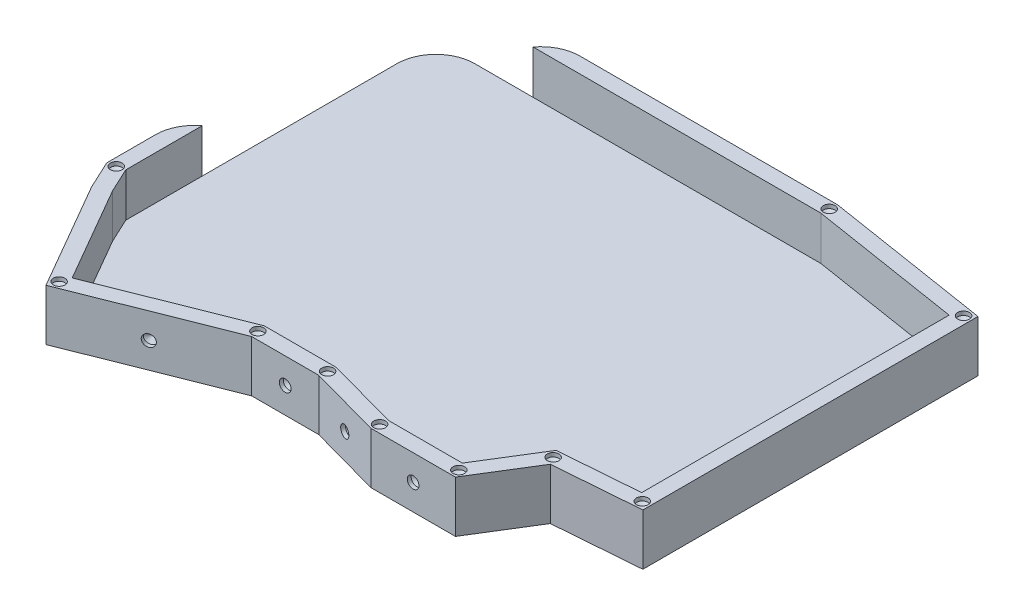
SolidWorks part; units mm, degrees
ref_plane "Front Plane" through (0, 0, 0) normal (0, 0, 1) x (1, 0, 0)
ref_plane "Top Plane" through (0, 0, 0) normal (0, 1, 0) x (1, 0, 0)
ref_plane "Right Plane" through (0, 0, 0) normal (1, 0, 0) x (0, 0, -1)
sketch "Sketch4"
  line L0 (261.3841, 490) -> (1306.7175, 490) construction
sketch "outline" plane through (0, 0, 0) normal (0, 1, 0) x (1, 0, 0)
  line L0 (23.1521, 111.8179) -> (23.1521, 32.6746) construction
  line L1 (23.1521, 32.6746) -> (26.0432, 26.4778) construction
  line L2 (26.0432, 26.4778) -> (40.0838, 2.1711) construction
  line L3 (40.0838, 2.1711) -> (75.1374, 16.0801) construction
  line L4 (75.1374, 16.0801) -> (93.8189, 16.0801) construction
  line L5 (93.8189, 16.0801) -> (112.2703, 10.9819) construction
  line L6 (112.2703, 10.9819) -> (130.9633, 10.9819) construction
  line L7 (130.9633, 10.9819) -> (140.1644, 25.8373) construction
  line L8 (140.1644, 25.8373) -> (160.3881, 27.4157) construction
  line L9 (160.3881, 27.4157) -> (160.3881, 105.6539) construction
  line L10 (160.3881, 105.6539) -> (121.5662, 111.8179) construction
  line L11 (121.5662, 111.8179) -> (23.1521, 111.8179) construction
  line L12 (22.7521, 112.2179) -> (22.7521, 32.5858)
  line L13 (22.7521, 32.5858) -> (25.6881, 26.2928)
  line L14 (25.6881, 26.2928) -> (39.9102, 1.6719)
  line L15 (39.9102, 1.6719) -> (75.2139, 15.6801)
  line L16 (75.2139, 15.6801) -> (93.7646, 15.6801)
  line L17 (93.7646, 15.6801) -> (112.216, 10.5819)
  line L18 (112.216, 10.5819) -> (131.1861, 10.5819)
  line L19 (131.1861, 10.5819) -> (140.3977, 25.4543)
  line L20 (140.3977, 25.4543) -> (160.7881, 27.0457)
  line L21 (160.7881, 27.0457) -> (160.7881, 105.9954)
  line L22 (160.7881, 105.9954) -> (121.5978, 112.2179)
  line L23 (121.5978, 112.2179) -> (22.7521, 112.2179)
  line L24 (18.7521, 116.2179) -> (18.7521, 31.6986)
  line L25 (18.7521, 31.6986) -> (22.1371, 24.4433)
  line L26 (22.1371, 24.4433) -> (38.1745, -3.3202)
  line L27 (38.1745, -3.3202) -> (75.9785, 11.6801)
  line L28 (75.9785, 11.6801) -> (93.2222, 11.6801)
  line L29 (93.2222, 11.6801) -> (111.6736, 6.5819)
  line L30 (111.6736, 6.5819) -> (133.4137, 6.5819)
  line L31 (133.4137, 6.5819) -> (142.7305, 21.6242)
  line L32 (142.7305, 21.6242) -> (164.7881, 23.3457)
  line L33 (164.7881, 23.3457) -> (164.7881, 109.4104)
  line L34 (164.7881, 109.4104) -> (121.9134, 116.2179)
  line L35 (121.9134, 116.2179) -> (18.7521, 116.2179)
  line L36 (23.9521, 111.0179) -> (23.9521, 32.852)
  line L37 (23.9521, 32.852) -> (26.7534, 26.8477)
  line L38 (26.7534, 26.8477) -> (40.431, 3.1695)
  line L39 (40.431, 3.1695) -> (74.9845, 16.8801)
  line L40 (74.9845, 16.8801) -> (93.9274, 16.8801)
  line L41 (93.9274, 16.8801) -> (112.3788, 11.7819)
  line L42 (112.3788, 11.7819) -> (130.5178, 11.7819)
  line L43 (130.5178, 11.7819) -> (139.6978, 26.6033)
  line L44 (139.6978, 26.6033) -> (159.5881, 28.1556)
  line L45 (159.5881, 28.1556) -> (159.5881, 104.9709)
  line L46 (159.5881, 104.9709) -> (121.5031, 111.0179)
  line L47 (121.5031, 111.0179) -> (23.9521, 111.0179)
  dimension "D1" = 137.236
  dimension "D3" = 4
  dimension "D4" = 1.2
  dimension "D2" = 0.4
extrude "Boss-Extrude1" add sketch "outline" along normal blind 13.2 contours L34 L35 L24 L25 L26 L27 L28 L29 L30 L31 L32 L33 L23 L22 L21 L20 L19 L18 L17 L16 L15 L14 L13 L12 region at (70.3327, 0, -114.3307)
extrude "Boss-Extrude3" add sketch "outline<4>" along normal blind 2 contours L22 L23 L12 L13 L14 L15 L16 L17 L18 L19 L20 L21 L47 L46 L45 L44 L43 L42 L41 L40 L39 L38 L37 L36 | L46 L47 L36 L37 L38 L39 L40 L41 L42 L43 L44 L45 region at (72.1749, 0, -112.0411) region at (89.8763, 0, -62.795)
sketch "outline<4>" plane through (0, 0, 0) normal (0, 1, 0) x (1, 0, 0) same geometry as "outline"
sketch "cutout" plane through (0, 0, 0) normal (0, 1, 0) x (1, 0, 0)
  line L0 (47.7521, 112.2179) -> (47.7521, 116.2179)
  line L1 (22.7521, 112.2179) -> (47.7521, 112.2179)
  line L2 (22.7521, 112.2179) -> (22.7521, 52.2179)
  line L3 (22.7521, 52.2179) -> (47.7521, 52.2179)
  line L4 (47.7521, 112.2179) -> (47.7521, 52.2179)
  line L6 (47.7521, 116.2179) -> (18.7521, 116.2179)
  line L7 (18.7521, 116.2179) -> (18.7521, 52.2179)
  line L9 (18.7521, 52.2179) -> (22.7521, 52.2179)
  dimension "D1" = 25
  dimension "D2" = 60
extrude "Cut-Extrude1" cut sketch "cutout" along normal through all contours L7 L9 L2 L1 L0 L6 region at (35.2521, 0, -112.9206)
sketch "Sketch15" plane through (6.331, 0, 15.9554) normal (0.3688, 0, 0.9295) x (0.9295, 0, -0.3688)
  line L0 (34.2587, 13.2) -> (74.9299, 0) construction
  point P6 (54.5943, 6.6)
sketch "Sketch16" plane through (0, 0, -11.6801) normal (0, 0, 1) x (1, 0, 0)
  line L0 (75.9785, 13.2) -> (93.2222, 0) construction
  point P6 (84.6003, 6.6)
sketch "Sketch17" plane through (9.6107, 0, -34.7825) normal (-0.2663, 0, 0.9639) x (0.9639, 0, 0.2663)
  line L0 (86.7445, 13.2) -> (105.8873, 0) construction
  point P6 (96.3159, 6.6)
sketch "Sketch18" plane through (0, 0, -6.5819) normal (0, 0, 1) x (1, 0, 0)
  line L0 (111.6736, 13.2) -> (133.4137, 0) construction
  point P6 (122.5436, 6.6)
hole_wizard "Ø3.0mm Dowel Hole6" positions "Sketch15" profile "Sketch20" hole size "Ø3.0" standard "ANSI Metric"
sketch "Sketch20" plane through (57.0765, 6.6, -4.18) normal (0, 1, 0) x (0.9295, 0, -0.3688)
  line L0 (0, 0) -> (0, 1.9013)
  line L1 (0, 1.9013) -> (1.5, 1)
  line L2 (1.5, 1) -> (1.5, 0)
  line L5 (1.5, 0) -> (0, 0)
  line L10 (0, 1.9013) -> (-1.5, 1) construction
  line L11 (0, -6.35) -> (0, 107.95) construction
  dimension "Hole Dia." = 3
  dimension "Hole Depth" = 1
  dimension "Drill Angle" = 118
hole_wizard "Ø3.0mm Dowel Hole7" positions "Sketch16" profile "Sketch21" hole size "Ø3.0" standard "ANSI Metric"
sketch "Sketch21" plane through (84.6003, 6.6, -11.6801) normal (1, 0, 0) x (0, -1, 0)
  line L0 (0, 0) -> (0, 1.9013)
  line L1 (0, 1.9013) -> (1.5, 1)
  line L2 (1.5, 1) -> (1.5, 0)
  line L5 (1.5, 0) -> (0, 0)
  line L10 (0, 1.9013) -> (-1.5, 1) construction
  line L11 (0, -6.35) -> (0, 107.95) construction
  dimension "Hole Dia." = 3
  dimension "Hole Depth" = 1
  dimension "Drill Angle" = 118
hole_wizard "Ø3.0mm Dowel Hole8" positions "Sketch17" profile "Sketch22" hole size "Ø3.0" standard "ANSI Metric"
sketch "Sketch22" plane through (102.4479, 6.6, -9.131) normal (0, 1, 0) x (0.9639, 0, 0.2663)
  line L0 (0, 0) -> (0, 1.9013)
  line L1 (0, 1.9013) -> (1.5, 1)
  line L2 (1.5, 1) -> (1.5, 0)
  line L5 (1.5, 0) -> (0, 0)
  line L10 (0, 1.9013) -> (-1.5, 1) construction
  line L11 (0, -6.35) -> (0, 107.95) construction
  dimension "Hole Dia." = 3
  dimension "Hole Depth" = 1
  dimension "Drill Angle" = 118
hole_wizard "Ø3.0mm Dowel Hole5" positions "Sketch18" profile "Sketch19" hole size "Ø3.0" standard "ANSI Metric"
sketch "Sketch19" plane through (122.5436, 6.6, -6.5819) normal (1, 0, 0) x (0, -1, 0)
  line L0 (0, 0) -> (0, 1.9013)
  line L1 (0, 1.9013) -> (1.5, 1)
  line L2 (1.5, 1) -> (1.5, 0)
  line L5 (1.5, 0) -> (0, 0)
  line L10 (0, 1.9013) -> (-1.5, 1) construction
  line L11 (0, -6.35) -> (0, 107.95) construction
  dimension "Hole Dia." = 3
  dimension "Hole Depth" = 1
  dimension "Drill Angle" = 118
sketch "Sketch29" plane through (0, 13.2, 0) normal (0, 1, 0) x (1, 0, 0)
  line L0 (18.7521, 31.6986) -> (22.7521, 32.5858) construction
  line L1 (22.7521, 32.5858) -> (38.1745, -3.3202) construction
  line L2 (38.1745, -3.3202) -> (39.9102, 1.6719) construction
  line L3 (39.9102, 1.6719) -> (75.9785, 11.6801) construction
  line L4 (75.9785, 11.6801) -> (75.2139, 15.6801) construction
  line L5 (75.2139, 15.6801) -> (93.2222, 11.6801) construction
  line L6 (93.2222, 11.6801) -> (93.7646, 15.6801) construction
  line L7 (93.7646, 15.6801) -> (111.6736, 6.5819) construction
  line L8 (111.6736, 6.5819) -> (112.216, 10.5819) construction
  line L9 (112.216, 10.5819) -> (133.4137, 6.5819) construction
  line L10 (133.4137, 6.5819) -> (131.1861, 10.5819) construction
  line L11 (131.1861, 10.5819) -> (142.7305, 21.6242) construction
  line L12 (142.7305, 21.6242) -> (140.3977, 25.4543) construction
  line L13 (140.3977, 25.4543) -> (164.7881, 23.3457) construction
  line L14 (164.7881, 23.3457) -> (160.7881, 27.0457) construction
  line L15 (160.7881, 27.0457) -> (164.7881, 109.4104) construction
  line L16 (164.7881, 109.4104) -> (160.7881, 105.9954) construction
  line L17 (160.7881, 105.9954) -> (121.9134, 116.2179) construction
  line L18 (121.9134, 116.2179) -> (121.5978, 112.2179) construction
  point P41 (20.7521, 32.1422)
  point P43 (39.0424, -0.8241)
  point P45 (75.5962, 13.6801)
  point P47 (93.4934, 13.6801)
  point P49 (111.9448, 8.5819)
  point P51 (132.2999, 8.5819)
  point P53 (141.5641, 23.5392)
  point P55 (162.7881, 25.1957)
  point P57 (162.7881, 107.7029)
  point P59 (121.7556, 114.2179)
hole_wizard "Ø3.0mm Dowel Hole9" positions "Sketch29" profile "Sketch31" hole size "Ø3.0" standard "ANSI Metric"
sketch "Sketch31" plane through (121.7556, 13.2, -114.2179) normal (1, 0, 0) x (0, 0, 1)
  line L0 (0, 0) -> (0, 1.9013)
  line L1 (0, 1.9013) -> (1.5, 1)
  line L2 (1.5, 1) -> (1.5, 0)
  line L5 (1.5, 0) -> (0, 0)
  line L10 (0, 1.9013) -> (-1.5, 1) construction
  line L11 (0, -6.35) -> (0, 107.95) construction
  dimension "Hole Dia." = 3
  dimension "Hole Depth" = 1
  dimension "Drill Angle" = 118
fillet "Fillet1" radius 10 1 edges at (22.7521, 1, -112.2179)
fillet "Fillet2" radius 10 1 edges at (47.7521, 6.6, -116.2179)
fillet "Fillet3" radius 10 1 edges at (18.7521, 6.6, -52.2179)
mirror "Mirror1" [suppressed] of bodies 123
delete or keep bodies "Body-Delete/Keep 1" [suppressed] type delete bodies bodies 123
